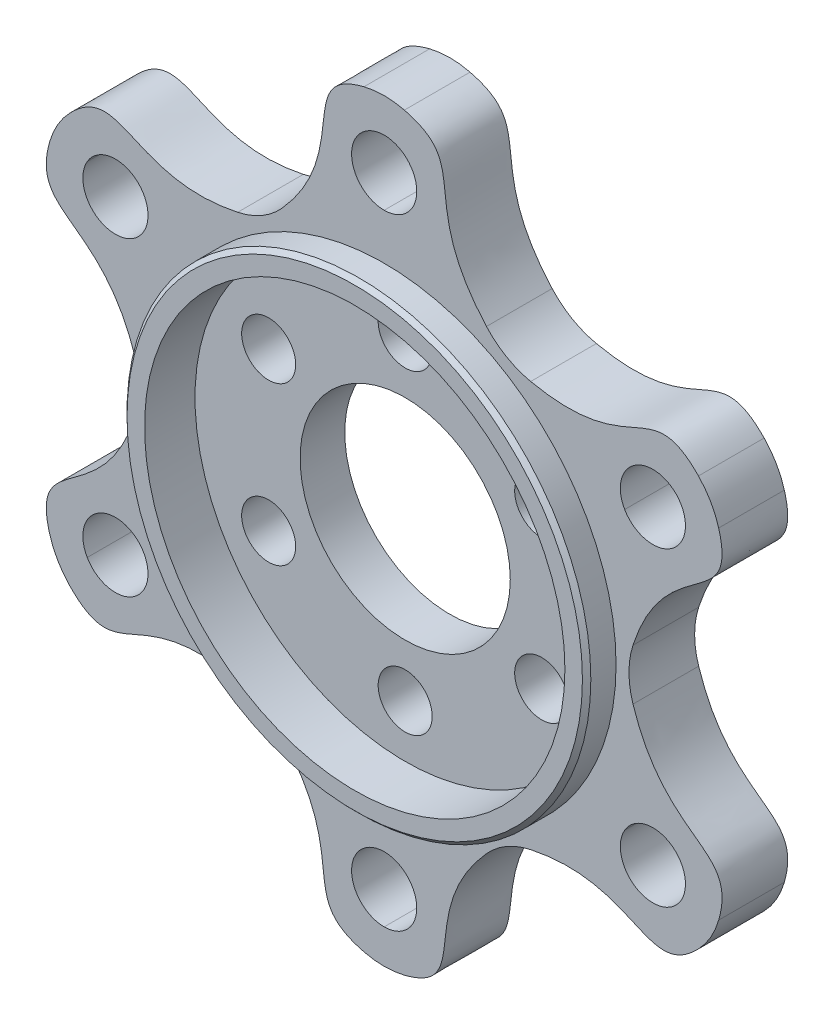
SolidWorks part; units mm, degrees
ref_plane "Front Plane" through (0, 0, 0) normal (0, 0, 1) x (1, 0, 0)
ref_plane "Top Plane" through (0, 0, 0) normal (0, 1, 0) x (1, 0, 0)
ref_plane "Right Plane" through (0, 0, 0) normal (1, 0, 0) x (0, 0, -1)
sketch "Sketch1" plane through (0, 0, 0) normal (0, 0, 1) x (1, 0, 0)
  line L0 (0, -55) -> (0, 55) construction
  line L1 (0, 0) -> (0, 45.72) construction
  circle A0 centre (0, 0) radius 12.7
  circle A1 centre (0, 0) radius 45.72
  circle A2 centre (0, 19.05) radius 3.2639
  circle A3 centre (16.4978, 9.525) radius 3.2639
  circle A4 centre (16.4978, -9.525) radius 3.2639
  circle A5 centre (0, -19.05) radius 3.2639
  circle A6 centre (-16.4978, -9.525) radius 3.2639
  circle A7 centre (-16.4978, 9.525) radius 3.2639
  circle A8 centre (0, 37.5) radius 3.937
  circle A10 centre (32.476, 18.75) radius 3.937
  circle A11 centre (32.476, -18.75) radius 3.937
  circle A12 centre (0, -37.5) radius 3.937
  circle A13 centre (-32.476, -18.75) radius 3.937
  circle A14 centre (-32.476, 18.75) radius 3.937
  point P21 (0, 0)
  point P36 (0, 0)
  dimension "D1" = 25.4
  dimension "D2" = 91.44
  dimension "D3" = 6.5278
  dimension "D6" = 7.874
  dimension "D4" = 19.05
  dimension "D8" = 37.5
  dimension "D5" = 6
  dimension "D7" = 6
extrude "Boss-Extrude3" add sketch "Sketch1" along normal blind 7.9375
sketch "Sketch2" plane through (0, 0, 7.9375) normal (0, 0, 1) x (1, 0, 0)
  line L0 (0, -55) -> (0, 55) construction
  line L1 (-32.476, 18.75) -> (0, 37.5) construction
  line L2 (-16.238, 28.125) -> (-6.35, 10.9985) construction
  line L3 (16.1981, 28.148) -> (6.3101, 11.0215) construction
  line L6 (32.476, -18.75) -> (32.476, 18.75) construction
  line L7 (32.476, 18.75) -> (0, 37.5) construction
  line L8 (55, 0) -> (-55, 0) construction
  circle A0 centre (0, 0) radius 27.94 construction
  circle A1 centre (0, 0) radius 45.72 construction
  circle A2 centre (0, 0) radius 12.7 construction
  circle A3 centre (0, 0) radius 45.72
  spline S0 degree 3 poles (-14.625, 25.3312) (-1.5745, 37.1177) (-13.1193, 43.9586) (0, 45.72) knots 0 0 0 0 1 1 1 1
  spline S1 degree 3 poles (14.625, 25.3312) (1.5745, 37.1177) (13.1193, 43.9586) (0, 45.72) knots 0 0 0 0 1 1 1 1
  spline S2 degree 3 poles (-29.25, 0) (-32.9321, 17.1953) (-44.6289, 10.6177) (-39.5947, 22.86) knots 0 0 0 0 1 1 1 1
  spline S3 degree 3 poles (-14.625, 25.3312) (-31.3576, 19.9224) (-31.5096, 33.3409) (-39.5947, 22.86) knots 0 0 0 0 1 1 1 1
  spline S4 degree 3 poles (-14.625, -25.3312) (-31.3576, -19.9224) (-31.5096, -33.3409) (-39.5947, -22.86) knots 0 0 0 0 1 1 1 1
  spline S5 degree 3 poles (-29.25, 0) (-32.9321, -17.1953) (-44.6289, -10.6177) (-39.5947, -22.86) knots 0 0 0 0 1 1 1 1
  spline S6 degree 3 poles (14.625, -25.3312) (31.3576, -19.9224) (31.5096, -33.3409) (39.5947, -22.86) knots 0 0 0 0 1 1 1 1
  spline S7 degree 3 poles (29.25, 0) (32.9321, -17.1953) (44.6289, -10.6177) (39.5947, -22.86) knots 0 0 0 0 1 1 1 1
  spline S8 degree 3 poles (14.625, -25.3312) (1.5745, -37.1177) (13.1193, -43.9586) (0, -45.72) knots 0 0 0 0 1 1 1 1
  spline S9 degree 3 poles (-14.625, -25.3312) (-1.5745, -37.1177) (-13.1193, -43.9586) (0, -45.72) knots 0 0 0 0 1 1 1 1
  spline S10 degree 3 poles (29.25, 0) (32.9321, 17.1953) (44.6289, 10.6177) (39.5947, 22.86) knots 0 0 0 0 1 1 1 1
  spline S11 degree 3 poles (14.625, 25.3312) (31.3576, 19.9224) (31.5096, 33.3409) (39.5947, 22.86) knots 0 0 0 0 1 1 1 1
  point P5 (-16.238, 28.125)
  point P6 (16.1981, 28.148)
  circle M8 centre (0, 0) radius 45.72
  dimension "D1" = 55.88
  dimension "D2" = 18.796
  dimension "D3" = 29.25
extrude "Cut-Extrude1" cut sketch "Sketch2" against normal blind 22.86 contours S1 S11 M8 | S5 S2 A3 | S10 S7 A3 | S6 S8 A3 | S9 S4 M8 | S3 S0 M8 region at (38.672, 0, 7.9375) region at (19.336, 33.4909, 7.9375) region at (19.336, -33.4909, 7.9375) region at (-19.336, 33.4909, 7.9375) region at (-19.336, -33.4909, 7.9375) region at (-38.672, 0, 7.9375)
sketch "Sketch4" plane through (0, 0, 7.9375) normal (0, 0, 1) x (1, 0, 0)
  circle A0 centre (0, 0) radius 12.7 construction
  circle A1 centre (0, 0) radius 12.7 construction
  circle A2 centre (0, 0) radius 28.025
  circle A3 centre (0, 0) radius 25.4
  dimension "D1" = 56.05
  dimension "D2" = 50.8
extrude "Boss-Extrude4" add sketch "Sketch4" along normal blind 3.556 contours A2 | A3
ref_plane "Plane1" through (0, 0, 0) normal (1, 0, 0) x (0, 0, -1)
ref_plane "Plane2" through (0, 0, 0) normal (-0.5, -0.866, 0) x (-0.866, 0.5, 0)
ref_plane "Plane3" through (0, 0, 0) normal (-0.5, 0.866, 0) x (0.866, 0.5, 0)
split line "Split Line1"
split line "Split Line2"
split line "Split Line3"
ref_axis "Axis1" through (0, 0, 7.9375) along (0, 0, -1)
fillet "Fillet1" radius 10 12 edges at (29.25, 0, 3.9688) (39.5947, -22.86, 3.9688) (0, -45.72, 3.9688) (14.625, -25.3312, 3.9688) (-14.625, -25.3312, 3.9688) (-39.5947, -22.86, 3.9688) (-29.25, 0, 3.9688) (-39.5947, 22.86, 3.9688) (-14.625, 25.3312, 3.9688) (14.625, 25.3312, 3.9688) (39.5947, 22.86, 3.9688) (0, 45.72, 3.9688)
chamfer "Chamfer1" distance 0.508 angle 45 1 edges at (28.025, 0, 11.4935)
sketch "Sketch7" plane through (0, 0, 7.9375) normal (0, 0, 1) x (1, 0, 0)
  circle A0 centre (0, 0) radius 25.4
extrude "Cut-Extrude2" cut sketch "Sketch7" against normal blind 2.54
